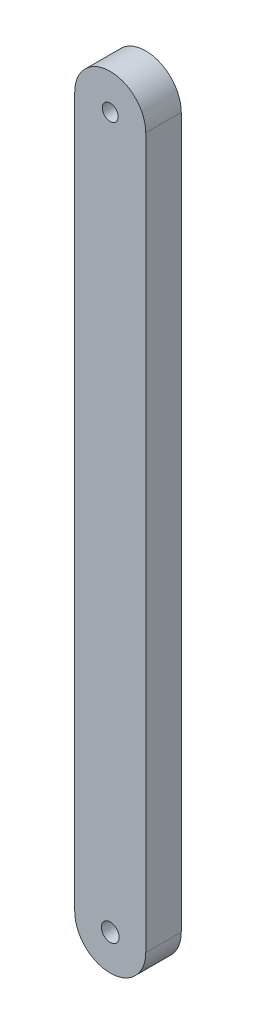
SolidWorks part; units mm, degrees
ref_plane "Front Plane" through (0, 0, 0) normal (0, 0, 1) x (1, 0, 0)
ref_plane "Top Plane" through (0, 0, 0) normal (0, 1, 0) x (1, 0, 0)
ref_plane "Right Plane" through (0, 0, 0) normal (1, 0, 0) x (0, 0, -1)
sketch "Sketch1" plane through (0, 0, 0) normal (0, 1, 0) x (1, 0, 0)
  line L0 (-10, 100) -> (10, 100) construction
  line L2 (10, -100) -> (10, 100)
  line L4 (-10, -100) -> (-10, 100)
  line L5 (10, -100) -> (-10, 100) construction
  line L6 (10, 100) -> (-10, -100) construction
  line L8 (-1.5875, 98.4125) -> (1.5875, 98.4125)
  line L9 (-1.5875, 98.4125) -> (-1.5875, 101.5875)
  line L10 (-1.5875, 101.5875) -> (1.5875, 101.5875)
  line L11 (1.5875, 98.4125) -> (1.5875, 101.5875)
  line L12 (-1.5875, 98.4125) -> (1.5875, 101.5875) construction
  line L13 (-1.5875, 101.5875) -> (1.5875, 98.4125) construction
  arc A0 (-10, 100) -> (10, 100) centre (0, 100) cw
  arc A1 (10, -100) -> (-10, -100) centre (0, -100) cw
  circle A2 centre (0, -100) radius 2.5
  circle A3 centre (0, 100) radius 2.2451
  point P0 (0, 0)
  dimension "D3" = 5
  dimension "D1" = 200
  dimension "D2" = 20
  dimension "D4" = 3.175
extrude "Boss-Extrude1" add sketch "Sketch1" along normal blind 10 contours A1 L2 A0 L4 A3 A2 region at (0, 0, -0.0888)
move or copy body "Body-Move/Copy1" bodies to move or copy 101 copy no rotation origin (0, 5, 0) rotation axis (1, 0, 0) rotation angle 90
